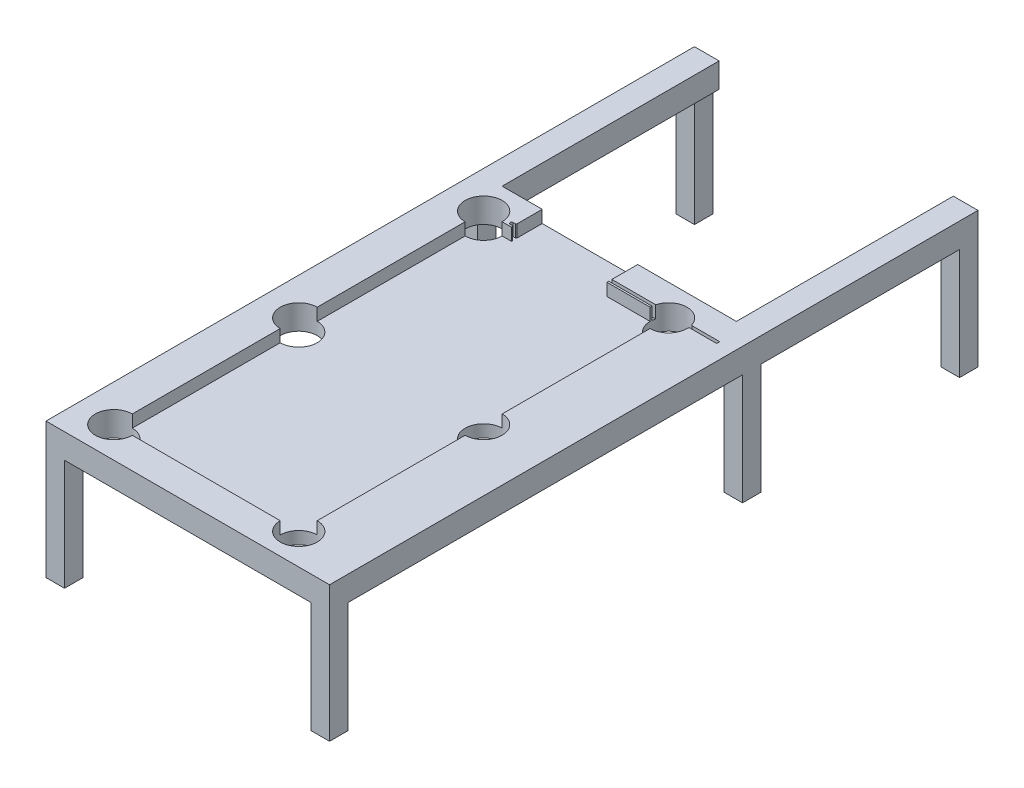
SolidWorks part; units mm, degrees
ref_plane "Front Plane" through (0, 0, 0) normal (0, 0, 1) x (1, 0, 0)
ref_plane "Top Plane" through (0, 0, 0) normal (0, 1, 0) x (1, 0, 0)
ref_plane "Right Plane" through (0, 0, 0) normal (1, 0, 0) x (0, 0, -1)
sketch "Sketch2" plane through (0, 0, 0) normal (0, 1, 0) x (1, 0, 0)
  line L1 (0, 0) -> (460, 0)
  line L2 (0, 0) -> (0, 700)
  line L3 (0, 700) -> (460, 700)
  line L4 (460, 0) -> (460, 700)
  line L5 (60, 50) -> (360, 50)
  line L6 (60, 50) -> (60, 650)
  line L7 (60, 650) -> (360, 650)
  line L8 (360, 50) -> (360, 650)
  dimension "D1" = 700
  dimension "D2" = 460
  dimension "D3" = 600
  dimension "D4" = 300
  dimension "D5" = 60
  dimension "D6" = 50
extrude "Boss-Extrude1" add sketch "Sketch2" along normal blind 20
ref_plane "Plane1" through (0, 0, -700) normal (0, 0, -1) x (-1, 0, 0)
sketch "Sketch10" plane through (0, 0, 0) normal (0, -1, 0) x (1, 0, 0)
  line L1 (0, 0) -> (460, 0)
  line L2 (0, 0) -> (0, -700)
  line L3 (0, -700) -> (460, -700)
  line L4 (460, 0) -> (460, -700)
extrude "Boss-Extrude6" add sketch "Sketch10" along normal blind 20
sketch "Sketch11" plane through (0, -20, 0) normal (0, -1, 0) x (1, 0, 0)
  line L1 (0, 0) -> (30, 0)
  line L2 (0, 0) -> (0, -30)
  line L3 (0, -30) -> (30, -30)
  line L4 (30, 0) -> (30, -30)
  line L5 (460, 0) -> (430, 0)
  line L6 (460, 0) -> (460, -30)
  line L7 (460, -30) -> (430, -30)
  line L8 (430, 0) -> (430, -30)
  line L9 (0, -700) -> (30, -700)
  line L10 (0, -700) -> (0, -670)
  line L11 (0, -670) -> (30, -670)
  line L12 (30, -700) -> (30, -670)
  line L13 (460, -700) -> (430, -700)
  line L14 (460, -700) -> (460, -670)
  line L15 (460, -670) -> (430, -670)
  line L16 (430, -700) -> (430, -670)
  dimension "D1" = 30
extrude "Boss-Extrude7" add sketch "Sketch11" along normal blind 180
sketch "Sketch14" plane through (0, 20, 0) normal (0, 1, 0) x (1, 0, 0)
  line L0 (22, 700) -> (-22, 700) construction
  line L1 (0, 700) -> (40, 700)
  line L2 (0, 700) -> (0, 1052)
  line L3 (0, 1052) -> (40, 1052)
  line L4 (40, 700) -> (40, 1052)
  line L5 (0, 700) -> (0, 0) construction
  line L6 (460, 0) -> (460, 700) construction
  line L7 (460, 700) -> (420, 700)
  line L8 (460, 700) -> (460, 1052)
  line L9 (460, 1052) -> (420, 1052)
  line L10 (420, 700) -> (420, 1052)
  line L11 (330, 1052) -> (390, 1052) construction
  dimension "D3" = 40
  dimension "D4" = 40
extrude "Boss-Extrude8" add sketch "Sketch14" against normal blind 40
sketch "Sketch15" plane through (0, -20, 0) normal (0, -1, 0) x (1, 0, 0)
  line L1 (460, -1052) -> (430, -1052)
  line L2 (460, -1052) -> (460, -1022)
  line L3 (460, -1022) -> (430, -1022)
  line L4 (430, -1052) -> (430, -1022)
  line L6 (0, -1052) -> (30, -1052)
  line L7 (0, -1052) -> (0, -1022)
  line L8 (0, -1022) -> (30, -1022)
  line L9 (30, -1052) -> (30, -1022)
  dimension "D1" = 30
  dimension "D2" = 30
  dimension "D3" = 30
  dimension "D4" = 30
extrude "Boss-Extrude9" add sketch "Sketch15" along normal blind 180
sketch "Sketch17" plane through (0, 20, 0) normal (0, 1, 0) x (1, 0, 0)
  line L0 (60, 650) -> (60, 50) construction
  line L1 (360, 50) -> (360, 650) construction
  circle A0 centre (60, 650) radius 30
  circle A1 centre (60, 350) radius 30
  circle A2 centre (60, 50) radius 30
  circle A3 centre (360, 50) radius 30
  circle A4 centre (360, 350) radius 30
  circle A5 centre (360, 650) radius 30
  line M15 (60, 50) -> (60, 650)
  line M16 (60, 650) -> (360, 650)
  line M17 (360, 650) -> (360, 50)
  line M18 (360, 50) -> (60, 50)
  dimension "D1" = 60
extrude "Cut-Extrude1" cut sketch "Sketch17" against normal blind 60 contours A5 M17 M16 | A4 M17 | A3 M18 M17 | A1 M15 | A1 M15 | A2 M15 M18 | A2 M18 M15 | A3 M17 M18 | A5 M16 M17 | A4 M17 | A0 region at (347.2676, 20, -637.2676) region at (364.2441, 20, -654.2441) region at (47.2676, 20, -350) region at (72.7324, 20, -350) region at (347.2676, 20, -350) region at (372.7324, 20, -350) region at (55.7559, 20, -45.7559) region at (72.7324, 20, -62.7324) region at (347.2676, 20, -62.7324) region at (364.2441, 20, -45.7559)
sketch "Sketch18" plane through (0, 20, 0) normal (0, 1, 0) x (1, 0, 0)
  line L9 (330, 650) -> (90, 650) construction
  line L10 (420, 700) -> (40, 700) construction
  line L11 (182.5, 700) -> (260, 700)
  line L12 (260, 700) -> (260, 650)
  line L13 (330, 650) -> (90, 650) construction
  line L14 (210, 650) -> (260, 650)
  line L15 (182.5, 700) -> (105, 700)
  line L16 (105, 700) -> (105, 650)
  line L17 (105, 650) -> (210, 650)
  dimension "D1" = 77.5
  dimension "D2" = 77.5
  dimension "D3" = 70
extrude "Cut-Extrude2" cut sketch "Sketch18" against normal blind 20
sketch "Sketch19" plane through (105, 0, 0) normal (1, 0, 0) x (0, 0, -1)
  line L0 (650, 0) -> (652.5, 0) construction
  line L1 (700, 0) -> (650, 0) construction
  line L2 (652.5, 0) -> (652.5, 2.5) construction
  line L4 (652.5, 2.5) -> (650, 2.5)
  line L5 (652.5, 2.5) -> (652.5, 0)
  line L6 (652.5, 0) -> (650, 0)
  line L7 (650, 2.5) -> (650, 0)
  point P8 (652.5, 2.5)
  dimension "D1" = 2.5
  dimension "D2" = 2.5
sketch "Sketch20" plane through (0, 20, 0) normal (0, 1, 0) x (1, 0, 0)
  line L0 (105, 650) -> (90, 650) construction
  line L1 (100, 658) -> (435, 658)
  line L2 (100, 658) -> (100, 653)
  line L3 (100, 653) -> (435, 653)
  line L4 (435, 658) -> (435, 653)
  circle A0 centre (100, 655.5) radius 2.5
  point P7 (0, 0)
  line M6 (105, 650) -> (105, 700)
  line M16 (260, 700) -> (260, 650)
  arc M18 (330, 650) -> (360, 620) centre (360, 650) cw
  dimension "D1" = 335
  dimension "D2" = 5
  dimension "D3" = 3
  dimension "D4" = 5
extrude "Cut-Extrude3" cut sketch "Sketch20" against normal blind 20 contours L2 A0 | A0 L3 L1 M6 | L3 L1 M6 M16 | L3 L1 M16 M18 | L4 L1 L3 M18 | A0 region at (103.4305, 20, -655.5) region at (98.939, 20, -655.5) region at (182.5, 20, -655.5) region at (295.2731, 20, -655.5055) region at (412.2267, 20, -655.5085)
chamfer "Chamfer1" distance 1 angle 45 4 edges at (105, 10, -653) (105, 10, -658) (389.8496, 10, -653) (388.9137, 10, -658) first distance on face at (102.5, 10, -653) first distance on face at (105, 10, -679) first distance on face at (360, -20, -680) first distance on face at (411.9568, 10, -658)
